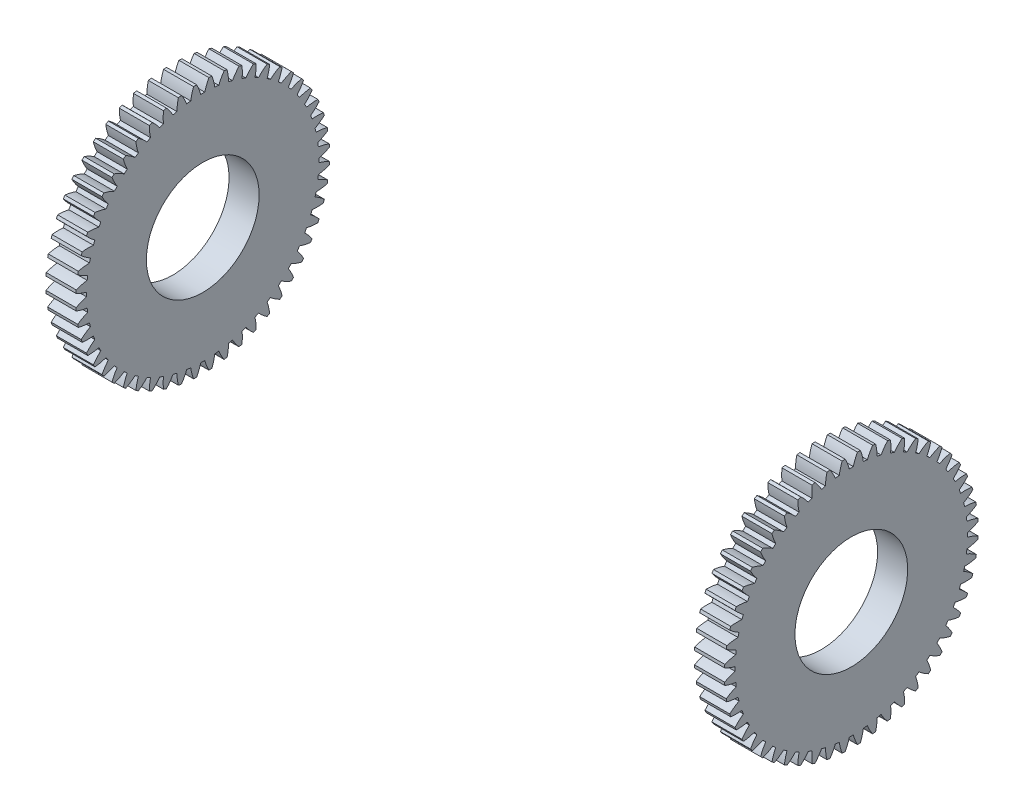
SolidWorks part; units mm, degrees
material "CF Nylon"
ref_plane "Plane1" through (0, 0, 0) normal (0, 0, 1) x (1, 0, 0)
ref_plane "Plane2" through (0, 0, 0) normal (0, 1, 0) x (1, 0, 0)
ref_plane "Plane3" through (0, 0, 0) normal (1, 0, 0) x (0, 0, -1)
other "Configuration Table"
sketch "HoldingSke" plane through (0, 0, 0) normal (0, 1, 0) x (1, 0, 0)
  line L0 (0, 0) -> (500.4096, -640.4951)
  line L1 (-15, 0) -> (100, 0) construction
  line L2 (0, 0) -> (-2.1039, 2.3779)
  line L3 (0, 0) -> (-11.863, 4.5341)
  line L4 (0, 0) -> (5.3169, 6.8053)
  line L5 (0, 0) -> (-47.5972, -17.7524)
  line L6 (0, 0) -> (-4.2111, -2.8413)
  line L7 (-2.1039, 2.3779) -> (8.8308, 51.9871)
  line L8 (-76.2, 54.61) -> (-75.184, 54.61)
  line L9 (-71.009, 38.7566) -> (-53.1078, 45.2721)
  line L10 (-76.2, 71.12) -> (104.1128, 71.12)
  line L11 (0, 0) -> (-5.08, 0)
  line L12 (-76.2, 101.6) -> (-76.1716, 101.6)
  line L13 (24.9733, 27.94) -> (52.9518, 28.4284)
  line L14 (24.9733, 27.94) -> (25.0241, 27.9398)
  line L15 (24.9733, 27.94) -> (100.4021, 29.52)
  circle A0 centre (0, 0) radius 0.3969
  circle A1 centre (0, 0) radius 19.6342
  circle A2 centre (0, 0) radius 38.1
  circle A3 centre (0, 0) radius 0.3969
  dimension "MHD" = 39.2684
  dimension "Hub_dia" = 76.2
  dimension "Bore" = 0.7937
  dimension "MBD" = 0.7937
  dimension "Num_teeth" = 52
  dimension "Pitch" = 812.8
  dimension "Overall_len" = 50.8
  dimension "Show_teeth" = 52
  dimension "Thickness" = 5.08
  dimension "OAL" = 50.8001
  dimension "T_dim" = 1.016
  dimension "Ap" = 20
  dimension "H" = 19.05
  dimension "Pitch_radius" = 180.3128
  dimension "Width" = 5.08
  dimension "Backlash" = 0.0284
  dimension "Addendum_fac" = 1
  dimension "Dedendum_fac" = 1.2
  dimension "Clearance_fac" = 0.2
  dimension "Dedendum_add" = 0.0508
sketch "BasProSke" plane through (0, 0, 0) normal (0, 1, 0) x (1, 0, 0)
  line L0 (-10, 0) -> (60, 0) construction
  line L1 (0, 0) -> (0, 21.4312)
  line L2 (0, 0) -> (5.08, 0)
  line L3 (5.08, 0) -> (5.08, 21.4312)
  line L4 (5.08, 21.4312) -> (0, 21.4312)
  dimension "Thickness" = 5.08
  dimension "Diameter" = 42.8625
revolve "Base-Revolve" add sketch "BasProSke" angle 360 about L0
sketch "TooCutSke" plane through (0, 0, 0) normal (1, 0, 0) x (0, 0, -1)
  line L1 (0, 0) -> (0, 107) construction
  line L2 (0, 0) -> (-0.6731, 20.6265) construction
  line L3 (0, 0) -> (-2.4912, 41.1838) construction
  line L4 (-0.6731, 20.6265) -> (-1.2456, 20.5919) construction
  arc A0 (0.3404, 19.6312) -> (-0.3404, 19.6312) centre (0, 0) ccw
  arc A1 (1.0518, 21.4309) -> (-1.0518, 21.4309) centre (0, 0) ccw
  circle A2 centre (0, 0) radius 20.6375 construction
  circle A3 centre (0, 0) radius 19.3929 construction
  arc A4 (-0.3404, 19.6312) -> (-1.0518, 21.4309) centre (-8.3202, 17.5174) ccw
  arc A5 (1.0518, 21.4309) -> (0.3404, 19.6312) centre (8.3202, 17.5174) ccw
  dimension "Root_dia" = 39.2684
  dimension "Overcut_dia" = 42.9133
  dimension "Pitch_dia" = 41.275
  dimension "Base_dia" = 38.7858
  dimension "Flank_rad" = 8.255
  dimension "Half_ang" = 3.462
  dimension "Half_CT" = 0.5735
extrude "ToothCut" cut sketch "TooCutSke" along normal through all
fillet "Breaks" [suppressed] radius 0.0159 tangent propagation no
fillet "RootFillets" [suppressed] radius 0.2095
pattern_circular "TeethCuts" count 52 every 6.923 about axis through (-10, 0, 0) along (1, 0, 0) of "ToothCut", "RootFillets", "Breaks"
sketch "HubNeaOneSke" plane through (0, 0, 0) normal (-1, 0, 0) x (0, 0, 1)
  circle A0 centre (0, 0) radius 19.6342
  dimension "Diameter" = 39.2684
extrude "HubNearOne" [suppressed] add sketch "HubNeaOneSke" along normal blind 45.7201
sketch "HubNeaBotSke" plane through (0, 0, 0) normal (-1, 0, 0) x (0, 0, 1)
  circle A0 centre (0, 0) radius 19.6342
  dimension "Diameter" = 39.2684
extrude "HubNearBoth" [suppressed] add sketch "HubNeaBotSke" along normal blind 22.86
ref_plane "FarPln" through (5.08, 0, 0) normal (1, 0, 0) x (0, 0, -1)
sketch "HubFarSke" plane through (5.08, 0, 0) normal (1, 0, 0) x (0, 0, -1)
  circle A0 centre (0, 0) radius 19.6342
  dimension "Diameter" = 39.2684
extrude "HubFar" [suppressed] add sketch "HubFarSke" along normal blind 22.86
sketch "BorSke" plane through (0, 0, 0) normal (1, 0, 0) x (0, 0, -1)
  circle A0 centre (0, 0) radius 9.525 construction
  circle A2 centre (0, 0) radius 9.525
extrude "Bore" cut sketch "BorSke" along normal mid plane 101.6001
sketch "KeySke" plane through (0, 0, 0) normal (1, 0, 0) x (0, 0, -1)
  line L0 (-0.127, 0) -> (-0.127, 0.6191)
  line L1 (-0.127, 0.6191) -> (0.127, 0.6191)
  line L2 (0.127, 0.6191) -> (0.127, 0)
  line L3 (0, 0) -> (0, 34) construction
  line L4 (-0.127, 0) -> (0.127, 0)
  dimension "Offset" = 0.6191
  dimension "Width" = 0.254
extrude "Keyway" [suppressed] cut sketch "KeySke" along normal mid plane 101.6001
pattern_circular "Keyway2" [suppressed] count 2 every 90 about axis through (-10, 0, 0) along (1, 0, 0) reverse direction yes
ref_plane "Plane4" through (-52.25, 0, 0) normal (1, 0, 0) x (0, 0, -1)
mirror "Mirror1" about plane through (-52.25, 0, 0) normal (1, 0, 0) of bodies 103 104
equation "' \"Pitch@HoldingSke\" = 4"
equation "' \"Num_teeth@HoldingSke\" = 12"
equation "' \"Ap@HoldingSke\" =  20"
equation "' \"Ap@HoldingSke\" = 20"
equation "' \"Width@HoldingSke\" = 0.5"
equation "' \"Hub_dia@HoldingSke\"= 1"
equation "' \"Hub_dia@HoldingSke\" = 1"
equation "' \"Overall_len@HoldingSke\" = 1.0"
equation "' \"Bore@HoldingSke\" = 0.75"
equation "' \"T_dim@HoldingSke\" = 0.85"
equation "' \"Width@KeySke\" = 0.25"
equation "' \"Show_teeth@HoldingSke\" = 13"
equation "' \"Backlash@HoldingSke\" = 0.009"
equation "' \"Addendum_fac@HoldingSke\" = 1.0"
equation "' \"Dedendum_fac@HoldingSke\" = 1.25"
equation "' \"Dedendum_add@HoldingSke\" = 0.00005"
equation "' \"Clearance_fac@HoldingSke\" = 0.25"
equation "' \"Pitch@HoldingSke\" = 0.5"
equation "' \"Num_teeth@HoldingSke\" = 23"
equation "' \"Show_teeth@HoldingSke\" = 23"
equation "' \"Backlash@HoldingSke\" = 0.0375"
equation "\"Overcut_dia@TooCutSke\" = (\"Num_teeth@HoldingSke\" + 2 * \"Addendum_fac@HoldingSke\") / \"Pitch@HoldingSke\" + 0.002"
equation "\"Pitch_dia@TooCutSke\" = \"Num_teeth@HoldingSke\" / \"Pitch@HoldingSke\""
equation "\"Base_dia@TooCutSke\" = \"Num_teeth@HoldingSke\" / \"Pitch@HoldingSke\" * cos((\"Ap@HoldingSke\"  * 3.14159265 / 180))"
equation "\"Root_dia@TooCutSke\" = (\"Num_teeth@HoldingSke\" + 2) / \"Pitch@HoldingSke\" - 2 * (\"Addendum_fac@HoldingSke\" + \"Dedendum_fac@HoldingSke\") / \"Pitch@HoldingSke\" - \"Dedendum_add@HoldingSke\" * 2"
equation "\"Half_ang@TooCutSke\" = 180 / \"Num_teeth@HoldingSke\""
equation "\"Half_CT@TooCutSke\" = \"Num_teeth@HoldingSke\" / \"Pitch@HoldingSke\" * sin((3.14159265 / 2 / \"Num_teeth@HoldingSke\")) / 2 - 7 * \"Backlash@HoldingSke\" / 4"
equation "\"Flank_rad@TooCutSke\" = \"Num_teeth@HoldingSke\" / \"Pitch@HoldingSke\" / 5"
equation "\"Radius@RootFillets\" = \"Clearance_fac@HoldingSke\" / \"Pitch@HoldingSke\" + \"Dedendum_add@HoldingSke\""
equation "\"Break_rad@Breaks\" = 0.02 / \"Pitch@HoldingSke\""
equation "\"Thickness@HoldingSke\" = \"Width@HoldingSke\""
equation "\"OAL@HoldingSke\" = \"Thickness@HoldingSke\""
equation "\"MHD@HoldingSke\" = (\"Num_teeth@HoldingSke\" + 2) / \"Pitch@HoldingSke\" - 2 * (\"Addendum_fac@HoldingSke\" + \"Dedendum_fac@HoldingSke\")  / \"Pitch@HoldingSke\" - \"Dedendum_add@HoldingSke\" * 2"
equation "\"MBD@HoldingSke\" = (\"Num_teeth@HoldingSke\" + 2) / \"Pitch@HoldingSke\" - 2 * (\"Addendum_fac@HoldingSke\" + \"Dedendum_fac@HoldingSke\")  / \"Pitch@HoldingSke\" - \"Dedendum_add@HoldingSke\" * 2 - 0.002"
equation "\"MHD@HoldingSke\" = ((sgn( \"MHD@HoldingSke\" - \"Hub_dia@HoldingSke\" )-1)*( \"MHD@HoldingSke\" - \"Hub_dia@HoldingSke\" ))/-2+ \"Hub_dia@HoldingSke\""
equation "\"MBD@HoldingSke\" = ((sgn( \"MBD@HoldingSke\" - \"Bore@HoldingSke\" )-1)*( \"MBD@HoldingSke\" - \"Bore@HoldingSke\" ))/-2+ \"Bore@HoldingSke\""
equation "\"OAL@HoldingSke\" = ((sgn( \"OAL@HoldingSke\" - \"Overall_len@HoldingSke\" )+1)*( \"OAL@HoldingSke\" - \"Overall_len@HoldingSke\" ))/2 + \"Overall_len@HoldingSke\" + 0.000002"
equation "\"Num_teeth@TeethCuts\" = int( \"Show_teeth@HoldingSke\" ) + 1"
equation "\"Num_teeth@TeethCuts\" = ((sgn( \"Num_teeth@TeethCuts\" - \"Num_teeth@HoldingSke\" )-1)*( \"Num_teeth@TeethCuts\" - \"Num_teeth@HoldingSke\" ))/-2+ \"Num_teeth@HoldingSke\""
equation "\"Num_teeth@TeethCuts\" = ((sgn( \"Num_teeth@TeethCuts\" - 2.0)+1)*( \"Num_teeth@TeethCuts\" - 2.0))/2 +2.0"
equation "\"Angle@TeethCuts\" = 360.0 / \"Num_teeth@HoldingSke\""
equation "\"Diameter@BasProSke\" = (\"Num_teeth@HoldingSke\" + 2 * \"Addendum_fac@HoldingSke\") / \"Pitch@HoldingSke\""
equation "\"Thickness@BasProSke\"  = \"Thickness@HoldingSke\""
equation "' \"Fillet_rad@BasProSke\" =  \"Thickness@HoldingSke\" * 0.05"
equation "' \"Fillet_rad@BasProSke\" = \"Thickness@HoldingSke\" * 0.05"
equation "\"MHD@HoldingSke\" = ((sgn( \"MHD@HoldingSke\" - \"Root_dia@TooCutSke\" )-1)*( \"MHD@HoldingSke\" - \"Root_dia@TooCutSke\" ))/-2+ \"Root_dia@TooCutSke\""
equation "\"Diameter@HubNeaOneSke\" = \"MHD@HoldingSke\""
equation "\"Length@HubNearOne\" = \"OAL@HoldingSke\" - \"Thickness@BasProSke\""
equation "\"Diameter@HubNeaBotSke\" = \"MHD@HoldingSke\""
equation "\"Length@HubNearBoth\" = ( \"OAL@HoldingSke\" - \"Thickness@BasProSke\" ) / 2.0"
equation "\"Thickness@FarPln\" = \"Thickness@BasProSke\""
equation "\"Diameter@HubFarSke\" = \"MHD@HoldingSke\""
equation "\"Length@HubFar\" = ( \"OAL@HoldingSke\" - \"Thickness@BasProSke\" ) / 2.0"
equation "\"D1@Bore\" = \"OAL@HoldingSke\" * 2.0"
equation "\"D1@Keyway\" = \"OAL@HoldingSke\" * 2.0"
equation "\"Offset@KeySke\" = \"T_dim@HoldingSke\" - \"MBD@HoldingSke\" / 2.0"
